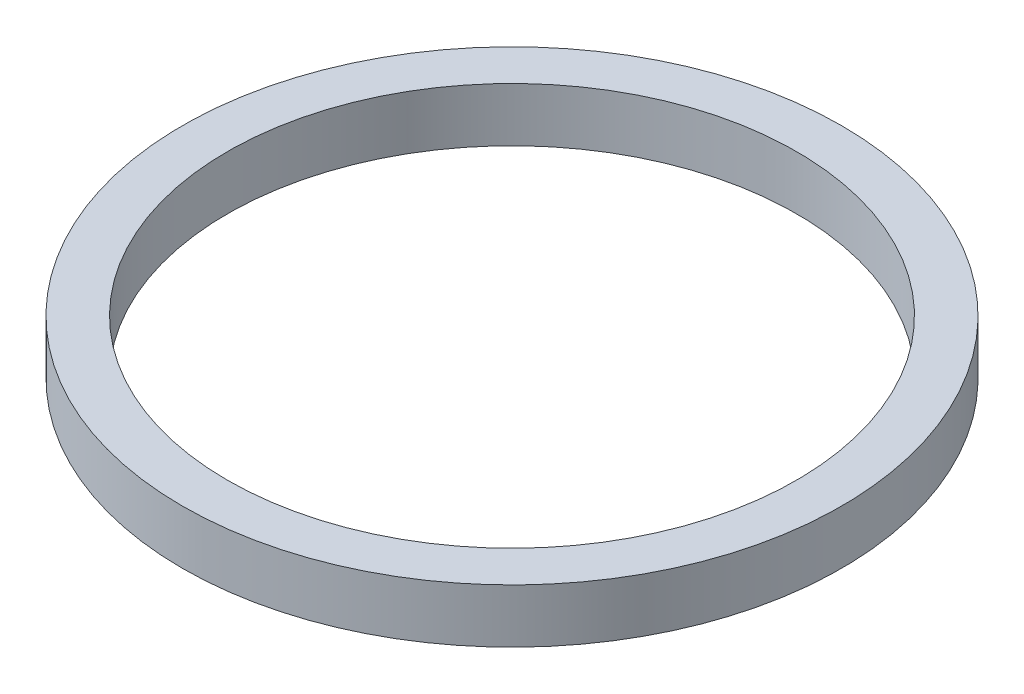
SolidWorks part; units mm, degrees
ref_plane "Front Plane" through (0, 0, 0) normal (0, 0, 1) x (1, 0, 0)
ref_plane "Top Plane" through (0, 0, 0) normal (0, 1, 0) x (1, 0, 0)
ref_plane "Right Plane" through (0, 0, 0) normal (1, 0, 0) x (0, 0, -1)
sketch "Sketch1" plane through (0, 0, 0) normal (0, 1, 0) x (1, 0, 0)
  circle A0 centre (0, 0) radius 55
  dimension "FLANGE_OD" = 110
extrude "Boss-Extrude1" add sketch "Sketch1" along normal blind 9
sketch "Sketch2" plane through (0, 0, 0) normal (0, 1, 0) x (1, 0, 0)
  circle A0 centre (0, 0) radius 47.5
  dimension "BORE_D" = 95
extrude "Cut-Extrude1" cut sketch "Sketch2" along normal through all
sketch "Sketch3" plane through (0, 9, 0) normal (0, 1, 0) x (1, 0, 0)
  circle A0 centre (0, 0) radius 25.6579 construction
  circle A1 centre (-25.6579, 0) radius 1.5
  dimension "BOLT_D" = 3
  dimension "BOLT_PCD" = 51.3158
extrude "Cut-Extrude2" cut sketch "Sketch3" against normal blind 7.522 rebuild error yes
pattern_circular "CirPattern1" count 8 over 360 rebuild error yes
